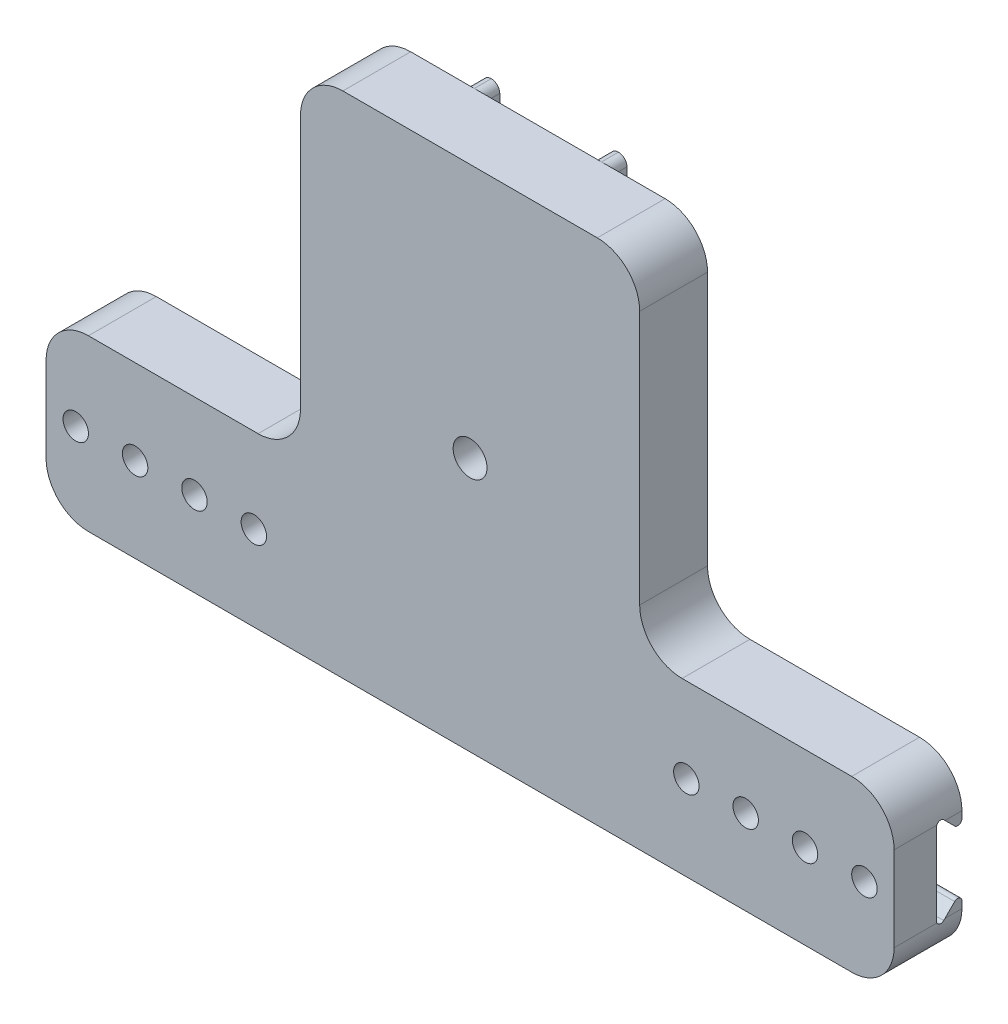
SolidWorks part; units mm, degrees
ref_plane "Front Plane" through (0, 0, 0) normal (0, 0, 1) x (1, 0, 0)
ref_plane "Top Plane" through (0, 0, 0) normal (0, 1, 0) x (1, 0, 0)
ref_plane "Right Plane" through (0, 0, 0) normal (1, 0, 0) x (0, 0, -1)
sketch "Sketch1" plane through (0, 0, 0) normal (0, 1, 0) x (1, 0, 0)
  line L1 (-20, 4) -> (20, 4)
  line L2 (-20, 4) -> (-20, -4)
  line L3 (-20, -4) -> (20, -4)
  line L4 (20, 4) -> (20, -4)
  line L5 (-20, 4) -> (20, -4) construction
  line L6 (-20, -4) -> (20, 4) construction
  point P0 (0, 0)
  dimension "D1" = 40
  dimension "D2" = 8
extrude "Boss-Extrude1" add sketch "Sketch1" against normal blind 60
sketch "Sketch2" plane through (20, 0, 0) normal (1, 0, 0) x (0, 0, -1)
  line L0 (-4, -60) -> (-4, 0) construction
  line L1 (4, -60) -> (-4, -60)
  line L2 (4, -60) -> (4, -40)
  line L3 (4, -40) -> (-4, -40)
  line L4 (-4, -60) -> (-4, -40)
  line L5 (0, -40) -> (0, -60) construction
  line L6 (4, -50) -> (-4, -50) construction
  point P532 (0, -50)
  dimension "D1" = 20
  dimension "D2" = 8
extrude "Boss-Extrude2" add sketch "Sketch2" along normal blind 30 contours L3 L4 L1 L2
sketch "Sketch3" plane through (50, 0, 0) normal (1, 0, 0) x (0, 0, -1)
  line L0 (1, -50) -> (1, -56)
  line L1 (1, -56) -> (4, -53)
  line L2 (4, -60) -> (4, -40) construction
  line L3 (1, -50) -> (1, -44)
  line L4 (1, -44) -> (4, -47)
  line L5 (4, -53) -> (4, -47)
  line L7 (4, -40) -> (-4, -40) construction
  dimension "D1" = 6
  dimension "D2" = 6
  dimension "D3" = 6
  dimension "D4" = 3
  dimension "D5" = 10
  dimension "D6" = 3
extrude "Cut-Extrude1" cut sketch "Sketch3" against normal blind 30 contours L0 L1 L5 L4 L3
sketch "Sketch6" plane through (0, 0, 4) normal (0, 0, 1) x (1, 0, 0)
  line L0 (50, -40) -> (20, -40) construction
  line L1 (50, -60) -> (50, -40) construction
  circle A0 centre (46.5, -50) radius 1.5
  dimension "D1" = 10
  dimension "D2" = 3
  dimension "D3" = 3.5
extrude "Cut-Extrude2" cut sketch "Sketch6" against normal through all contours A0
pattern_linear "LPattern1" count 4 spacing 7 along (-1, 0, 0) of "Cut-Extrude2"
mirror "Mirror3" about plane through (0, 0, 0) normal (1, 0, 0) of "LPattern1", "Cut-Extrude1", "Boss-Extrude2"
sketch "Sketch7" plane through (0, 0, 4) normal (0, 0, 1) x (1, 0, 0)
  circle A0 centre (0, -30) radius 2
  dimension "D1" = 30
extrude "Cut-Extrude3" cut sketch "Sketch7" against normal blind 30
sketch "Sketch8" plane through (0, 0, -4) normal (0, 0, -1) x (-1, 0, 0)
  line L0 (-20, 0) -> (20, 0) construction
  line L1 (-50, -60) -> (50, -60) construction
  line L2 (-8.5, 0) -> (-6.5, 0)
  line L3 (-8.5, 0) -> (-8.5, -60)
  line L4 (-8.5, -60) -> (-6.5, -60)
  line L5 (-6.5, 0) -> (-6.5, -60)
  line L6 (-7.5, -60) -> (-7.5, 0) construction
  line L7 (-8.5, -30) -> (-6.5, -30) construction
  line L9 (-20, -40) -> (-20, 0) construction
  point P662 (-7.5, -30)
  dimension "D1" = 2
  dimension "D2" = 12.5
extrude "Boss-Extrude3" add sketch "Sketch8" along normal blind 2
fillet "Fillet1" radius 1 2 edges at (8.5, 0, -5) (6.5, 0, -5)
mirror "Mirror4" about plane through (0, 0, 0) normal (1, 0, 0) of "Fillet1", "Boss-Extrude3"
fillet "Fillet2" radius 0.5 8 edges at (-35, -56, -1) (-35, -44, -1) (-35, -53, -4) (-35, -47, -4) (35, -44, -1) (35, -56, -1) (35, -53, -4) (35, -47, -4)
fillet "Fillet3" radius 5 8 edges at (-20, 0, 0) (20, 0, 0) (20, -40, 0) (-20, -40, 0) (-50, -60, 0) (-50, -40, 0) (50, -60, 0) (50, -40, 0)
